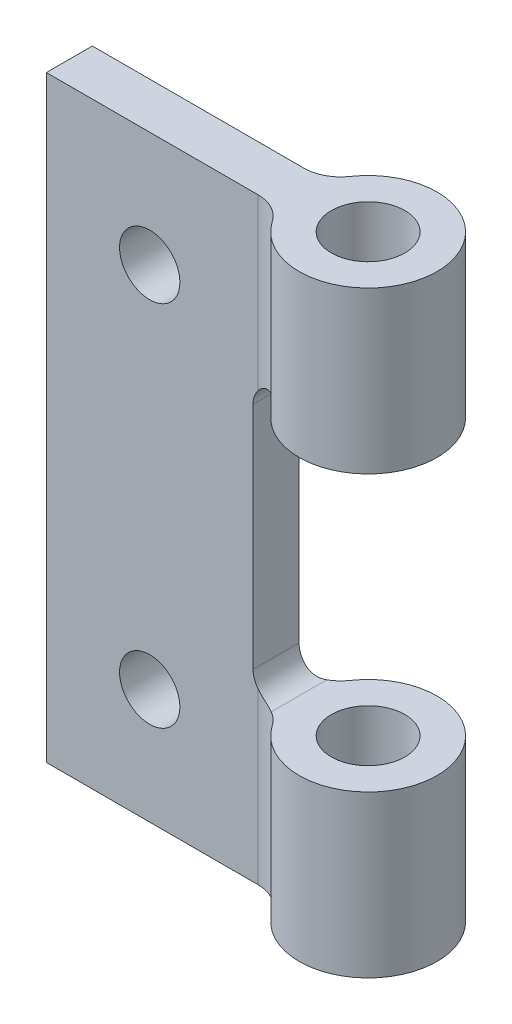
SolidWorks part; units mm, degrees
ref_plane "Front Plane" through (0, 0, 0) normal (0, 0, 1) x (1, 0, 0)
ref_plane "Top Plane" through (0, 0, 0) normal (0, 1, 0) x (1, 0, 0)
ref_plane "Right Plane" through (0, 0, 0) normal (1, 0, 0) x (0, 0, -1)
sketch "Sketch1" plane through (0, 0, 0) normal (0, 0, 1) x (1, 0, 0)
  line L0 (0, 0) -> (25.4, 0)
  line L1 (25.4, 0) -> (25.4, 11.1252)
  line L2 (25.4, 11.1252) -> (15.8623, 11.1252)
  line L3 (14.2748, 12.7127) -> (14.2748, 28.5623)
  line L4 (15.8623, 30.1498) -> (25.4, 30.1498)
  line L5 (25.4, 30.1498) -> (25.4, 41.275)
  line L6 (25.4, 41.275) -> (0, 41.275)
  line L7 (0, 41.275) -> (0, 0)
  line L8 (0, 0) -> (-0.3588, 0.2659)
  arc A0 (14.2748, 28.5623) -> (15.8623, 30.1498) centre (15.8623, 28.5623) cw
  arc A1 (15.8623, 11.1252) -> (14.2748, 12.7127) centre (15.8623, 12.7127) cw
  point P14 (14.2748, 11.1252)
  dimension "D6" = 1.5875
  dimension "D1" = 25.4
  dimension "D2" = 41.275
  dimension "D3" = 11.1252
  dimension "D4" = 11.1252
  dimension "D5" = 11.1252
extrude "Boss-Extrude1" add sketch "Sketch1" along normal mid plane 3.175 contours L2 A1 L3 A0 L4 L5 L6 L7 L0 L1
ref_plane "Plane1" through (0, 41.275, 0) normal (0, 1, 0) x (-1, 0, 0)
sketch "Sketch2" plane through (0, 41.275, 0) normal (0, 1, 0) x (-1, 0, 0)
  line L0 (-25.4, 0) -> (-20.6375, 0) construction
  line L1 (-25.4, 1.5875) -> (-25.4, -1.5875) construction
  dimension "D1" = 4.7625
ref_plane "Plane2" through (20.6375, 0, 0) normal (1, 0, 0) x (0, 0, -1)
other "SurfaceCut2"
sketch "Sketch3" plane through (0, 41.275, 0) normal (0, 1, 0) x (-1, 0, 0)
  circle A0 centre (-20.6375, 0) radius 4.7625
extrude "Boss-Extrude2" add sketch "Sketch3" against normal up to vertex (11.1252 mm away) up to point (20.6375, 30.1498, 1.5875)
ref_plane "Plane3" through (0, 11.1252, 0) normal (0, 1, 0) x (-1, 0, 0)
sketch "Sketch4" plane through (0, 11.1252, 0) normal (0, 1, 0) x (-1, 0, 0)
  line L0 (-20.6375, 0) -> (-25.4, 0) construction
  line L1 (-20.6375, -1.5875) -> (-20.6375, 1.5875) construction
  circle A0 centre (-20.6375, 0) radius 4.7625
  dimension "D1" = 4.7625
extrude "Boss-Extrude3" add sketch "Sketch4" against normal up to vertex (11.1252 mm away) up to point (20.6375, 0, 1.5875)
fillet "Fillet1" radius 2.54 4 edges at (16.1474, 5.5626, -1.5875) (16.1474, 35.7124, -1.5875) (16.1474, 5.5626, 1.5875) (16.1474, 35.7124, 1.5875)
sketch "Sketch5" plane through (0, 41.275, 0) normal (0, 1, 0) x (-1, 0, 0)
  circle A0 centre (-20.6375, 0) radius 2.54
extrude "Cut-Extrude1" cut sketch "Sketch5" against normal through all
ref_plane "Plane4" through (0, 0, 1.5875) normal (0, 0, 1) x (1, 0, 0)
sketch "Sketch6" plane through (0, 0, 1.5875) normal (0, 0, 1) x (1, 0, 0)
  line L0 (0, 20.6375) -> (14.2748, 20.6375) construction
  line L1 (0, 41.275) -> (0, 0) construction
  line L2 (14.2748, 12.7127) -> (14.2748, 28.5623) construction
  line L3 (7.1374, 20.6375) -> (7.1374, 33.3375) construction
  circle A0 centre (7.1374, 33.3375) radius 2.083
  circle A1 centre (7.1374, 7.9375) radius 2.083
  dimension "D1" = 12.7
extrude "Cut-Extrude2" cut sketch "Sketch6" against normal through all
